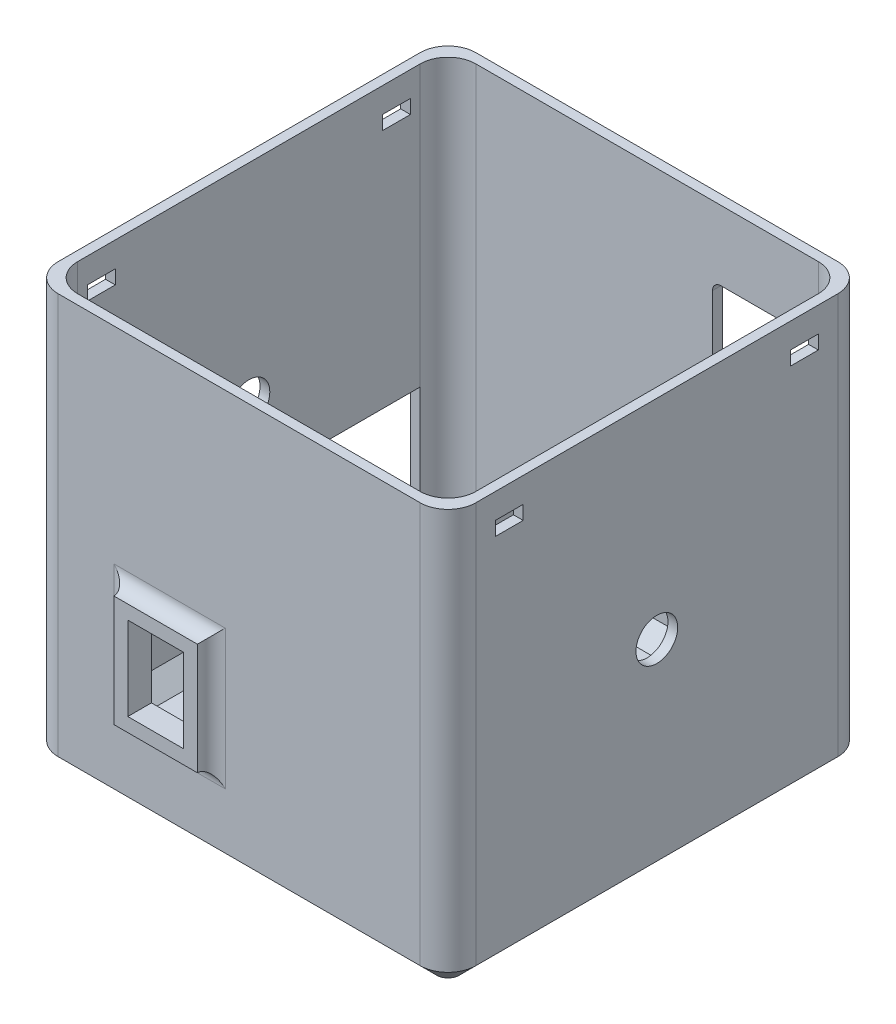
SolidWorks part; units mm, degrees
ref_plane "Front Plane" through (0, 0, 0) normal (0, 0, 1) x (1, 0, 0)
ref_plane "Top Plane" through (0, 0, 0) normal (0, 1, 0) x (1, 0, 0)
ref_plane "Right Plane" through (0, 0, 0) normal (1, 0, 0) x (0, 0, -1)
sketch "Sketch1" plane through (0, 0, 0) normal (0, 1, 0) x (1, 0, 0)
  line L1 (0, 0) -> (150, 0)
  line L2 (0, 0) -> (0, 150)
  line L3 (0, 150) -> (150, 150)
  line L4 (150, 0) -> (150, 150)
  dimension "D1" = 150
  dimension "D2" = 150
extrude "Boss-Extrude1" add sketch "Sketch1" along normal blind 150
shell "Shell1" thickness 3.5 removed face at (75, 150, -75)
fillet "Fillet2" radius 10 3 edges at (150, 75, -150) (150, 75, 0) (0, 75, 0)
fillet "Fillet3" radius 10 5 edges at (3.5, 76.75, -3.5) (146.5, 76.75, -3.5) (0, 75, -150) (146.5, 76.75, -146.5) (3.5, 76.75, -146.5)
sketch "Sketch2" plane through (150, 0, 0) normal (1, 0, 0) x (0, 0, -1)
  line L1 (150, 150) -> (150, 0) construction
  line L2 (10, 0) -> (140, 0) construction
  circle A0 centre (75, 75) radius 7.5
  dimension "D1" = 15
  dimension "D2" = 75
  dimension "D3" = 75
extrude "Cut-Extrude1" cut sketch "Sketch2" against normal blind 200
chamfer "Chamfer1" distance 6 angle 45 8 edges at (75, 0, 0) (0, 0, -75) (75, 0, -150) (2.9289, 0, -2.9289) (2.9289, 0, -147.0711) (147.0711, 0, -2.9289) (147.0711, 0, -147.0711) (150, 0, -75)
chamfer "Chamfer2" distance 6 angle 45 8 edges at (146.5, 3.5, -75) (75, 3.5, -146.5) (75, 3.5, -3.5) (143.5711, 3.5, -143.5711) (143.5711, 3.5, -6.4289) (6.4289, 3.5, -143.5711) (6.4289, 3.5, -6.4289) (3.5, 3.5, -75)
sketch "Sketch3" plane through (0, 0, 0) normal (-1, 0, 0) x (0, 0, 1)
  line L0 (-140, 150) -> (-10, 150) construction
  line L1 (-133, 141) -> (-123, 141)
  line L2 (-133, 141) -> (-133, 136)
  line L3 (-133, 136) -> (-123, 136)
  line L4 (-123, 141) -> (-123, 136)
  line L5 (-150, 6) -> (-150, 150) construction
  dimension "D1" = 10
  dimension "D2" = 5
  dimension "D3" = 9
  dimension "D4" = 17
extrude "Cut-Extrude2" cut sketch "Sketch3" against normal blind 234
sketch "Sketch4" plane through (0, 0, 0) normal (-1, 0, 0) x (0, 0, 1)
  line L0 (-140, 150) -> (-10, 150) construction
  line L1 (-17, 141) -> (-27, 141)
  line L2 (-17, 141) -> (-17, 136)
  line L3 (-17, 136) -> (-27, 136)
  line L4 (-27, 141) -> (-27, 136)
  line L5 (0, 150) -> (0, 6) construction
  dimension "D1" = 10
  dimension "D2" = 5
  dimension "D3" = 9
  dimension "D4" = 17
extrude "Cut-Extrude3" cut sketch "Sketch4" against normal blind 234
sketch "Sketch5" plane through (0, 3.5, 0) normal (0, 1, 0) x (1, 0, 0)
  line L0 (140.5, 13.5) -> (140.5, 136.5) construction
  line L1 (140.5, 100.5) -> (100.5, 100.5)
  line L2 (140.5, 100.5) -> (140.5, 140.5)
  line L3 (140.5, 140.5) -> (100.5, 140.5)
  line L4 (100.5, 100.5) -> (100.5, 140.5)
  line L5 (136.5, 140.5) -> (13.5, 140.5) construction
  dimension "D1" = 40
  dimension "D2" = 40
  dimension "D3" = 0
  dimension "D4" = 0
extrude "Cut-Extrude4" cut sketch "Sketch5" against normal blind 10
sketch "Sketch6" plane through (0, 3.5, 0) normal (0, 1, 0) x (1, 0, 0)
  line L0 (13.5, 146.5) -> (136.5, 146.5) construction
  line L1 (44.5, 101.5) -> (48.5, 101.5)
  line L2 (44.5, 101.5) -> (44.5, 146.5)
  line L3 (44.5, 146.5) -> (48.5, 146.5)
  line L4 (48.5, 101.5) -> (48.5, 146.5)
  line L6 (9.5, 136.5) -> (9.5, 13.5) construction
  dimension "D1" = 45
  dimension "D2" = 4
  dimension "D3" = 35
extrude "Boss-Extrude2" add sketch "Sketch6" along normal blind 40
fillet "Fillet4" radius 10 2 edges at (48.5, 26.5, -146.5) (48.5, 3.5, -121)
sketch "Sketch7" plane through (3.5, 0, 0) normal (1, 0, 0) x (0, 0, -1)
  line L1 (136.5, 9.5) -> (96.5, 9.5)
  line L2 (136.5, 9.5) -> (136.5, 49.5)
  line L3 (136.5, 49.5) -> (96.5, 49.5)
  line L4 (96.5, 9.5) -> (96.5, 49.5)
  dimension "D1" = 40
  dimension "D2" = 40
extrude "Cut-Extrude5" cut sketch "Sketch7" against normal blind 40
sketch "Sketch8" plane through (0, 0, -146.5) normal (0, 0, 1) x (1, 0, 0)
  line L0 (136.5, 9.5) -> (136.5, 150) construction
  line L1 (98.5, 97) -> (136.5, 97)
  line L2 (98.5, 97) -> (98.5, 125)
  line L3 (98.5, 125) -> (136.5, 125)
  line L4 (136.5, 97) -> (136.5, 125)
  line L5 (136.5, 150) -> (13.5, 150) construction
  dimension "D1" = 28
  dimension "D2" = 38
  dimension "D3" = 0
  dimension "D4" = 25
extrude "Cut-Extrude6" cut sketch "Sketch8" against normal blind 10
fillet "Fillet5" radius 3 4 edges at (136.5, 125, -148.25) (98.5, 97, -148.25) (98.5, 125, -148.25) (136.5, 97, -148.25)
sketch "Sketch9" plane through (0, 0, 0) normal (0, 0, 1) x (1, 0, 0)
  line L0 (10, 6) -> (140, 6) construction
  line L1 (35, 31) -> (65, 31)
  line L2 (35, 31) -> (35, 71)
  line L3 (35, 71) -> (65, 71)
  line L4 (65, 31) -> (65, 71)
  line L5 (10, 150) -> (10, 6) construction
  dimension "D1" = 40
  dimension "D2" = 30
  dimension "D3" = 25
  dimension "D4" = 25
extrude "Boss-Extrude3" add sketch "Sketch9" along normal blind 5 contours L2 L3 L4 L1
fillet "Fillet6" radius 5 4 edges at (35, 51, 0) (50, 31, 0) (65, 51, 0) (50, 71, 0)
sketch "Sketch11" plane through (0, 0, 5) normal (0, 0, 1) x (1, 0, 0)
  line L0 (65, 31) -> (65, 71) construction
  line L1 (40, 36) -> (60, 36)
  line L2 (40, 36) -> (40, 66)
  line L3 (40, 66) -> (60, 66)
  line L4 (60, 36) -> (60, 66)
  line L5 (35, 71) -> (65, 71) construction
  dimension "D1" = 30
  dimension "D2" = 20
  dimension "D3" = 5
  dimension "D4" = 5
extrude "Cut-Extrude9" cut sketch "Sketch11" against normal blind 20
